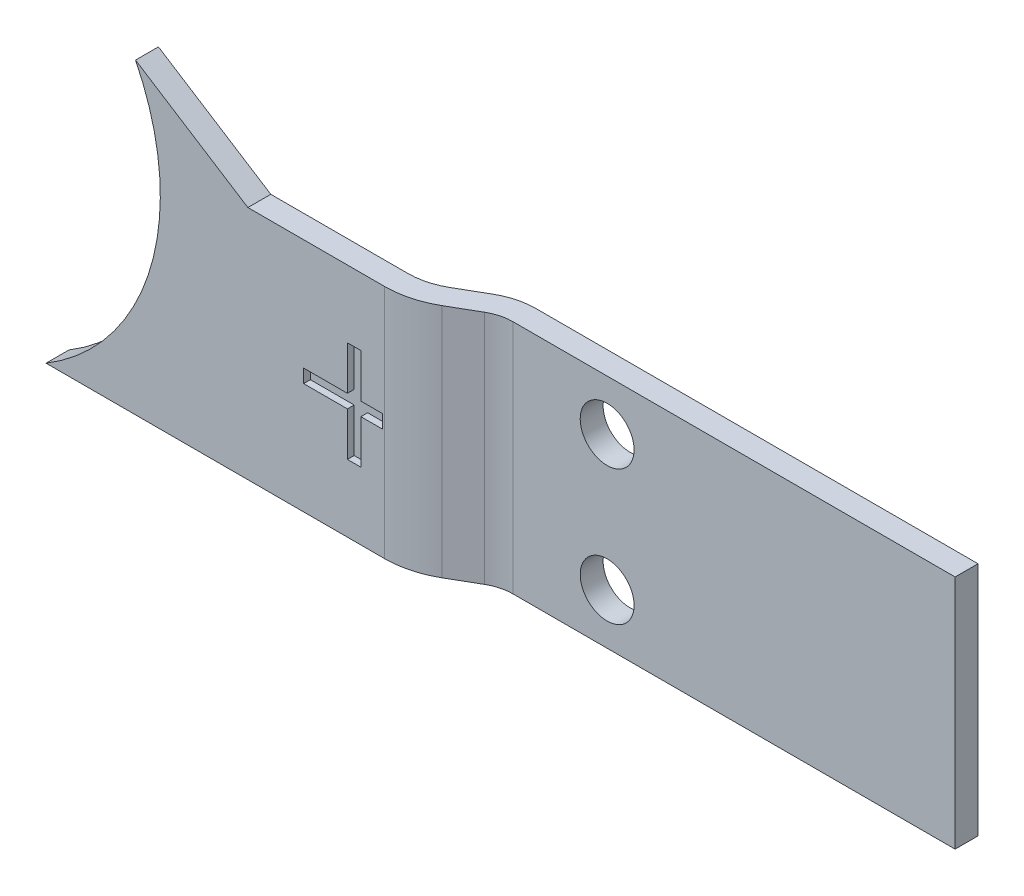
SolidWorks part; units mm, degrees
ref_plane "前视基准面" through (0, 0, 0) normal (0, 0, 1) x (1, 0, 0)
ref_plane "上视基准面" through (0, 0, 0) normal (0, 1, 0) x (1, 0, 0)
ref_plane "右视基准面" through (0, 0, 0) normal (1, 0, 0) x (0, 0, -1)
sketch "Sketch1" plane through (0, 0, 0) normal (0, 0, 1) x (1, 0, 0)
  line L0 (0, -30) -> (80, -30)
  line L1 (80, -30) -> (80, 5)
  line L2 (80, 5) -> (48, 5)
  line L4 (48, 5) -> (16.1141, 25.3049)
  arc A0 (16.1141, 25.3049) -> (0, -30) centre (0, 0) ccw
  dimension "D1" = 80
  dimension "D2" = 60
  dimension "D3" = 35
  dimension "D4" = 32
extrude "Boss-Extrude1" add sketch "Sketch1" along normal blind 3.4
sketch "Sketch2" plane through (0, 0, 3.4) normal (0, 0, 1) x (1, 0, 0)
  circle A0 centre (48, -12.5) radius 2.75
  circle A3 centre (48, -12.5) radius 2
  dimension "D2" = 5.5
sketch "Sketch3" plane through (0, 0, 3.4) normal (0, 0, 1) x (1, 0, 0)
  circle A0 centre (0, 0) radius 5
  dimension "D1" = 10
extrude "Cut-Extrude1" cut sketch "Sketch3" against normal blind 6
sketch "Sketch5" plane through (0, 0, 3.4) normal (0, 0, 1) x (1, 0, 0)
  line L0 (0, 20) -> (0, 0) construction
  line L1 (0, 0) -> (-18.1865, -10.5) construction
  arc A0 (0, 10) -> (-8.6603, -5) centre (0, 0) ccw
  arc A2 (0, 18) -> (-15.5885, -9) centre (0, 0) ccw
  arc A3 (-8.6603, -5) -> (-15.5885, -9) centre (-12.1244, -7) cw
  arc A4 (0, 18) -> (0, 10) centre (0, 14) cw
  point P4 (0, 18)
  point P6 (0, 10)
  point P8 (-8.6603, -5)
  point P9 (-15.5885, -9)
  dimension "D1" = 120
  dimension "D2" = 21
extrude "Cut-Extrude2" cut sketch "Sketch5" against normal blind 10
sketch "Sketch6" plane through (0, 0, 0) normal (0, 0, -1) x (-1, 0, 0)
  circle A0 centre (0, 0) radius 35
extrude "Cut-Extrude3" cut sketch "Sketch6" against normal blind 10
sketch "Sketch7" plane through (0, 0, 3.4) normal (0, 0, 1) x (1, 0, 0)
  line L0 (62.7754, -13.5) -> (62.7754, -20)
  line L1 (64.7754, -5) -> (62.7754, -5)
  line L2 (64.7754, -5) -> (64.7754, -11.5)
  line L3 (64.7754, -20) -> (62.7754, -20)
  line L4 (62.7754, -5) -> (62.7754, -11.5)
  line L5 (80, 5) -> (48, 5) construction
  line L7 (80, -30) -> (80, 5) construction
  line L8 (62.7754, -11.5) -> (56.2754, -11.5)
  line L9 (71.2754, -11.5) -> (64.7754, -11.5)
  line L10 (71.2754, -11.5) -> (71.2754, -13.5)
  line L11 (71.2754, -13.5) -> (64.7754, -13.5)
  line L12 (56.2754, -11.5) -> (56.2754, -13.5)
  line L17 (62.7754, -13.5) -> (56.2754, -13.5)
  line L18 (63.9087, -13.5) -> (63.642, -13.5)
  line L19 (64.7754, -13.5) -> (64.7754, -20)
  point P0 (63.9087, -12.5)
  point P9 (80, -12.5)
  point P10 (63.7754, -13.5)
  dimension "D1" = 15
  dimension "D2" = 2
  dimension "D3" = 0
  dimension "D4" = 2
  dimension "D5" = 15
  dimension "D6" = 16.5
extrude "Cut-Extrude4" cut sketch "Sketch7" against normal blind 1 contours L19 L11 L10 L9 L2 L1 L4 L8 L12 L17 L0 L3 region at (63.7754, -12.5, 3.4)
sketch "Sketch8" plane through (0, 0, 0) normal (0, 0, -1) x (-1, 0, 0)
  line L0 (-80, 5) -> (-48, 5) construction
  line L1 (-80, -30) -> (-68, -30)
  line L2 (-80, -30) -> (-80, 5)
  line L3 (-80, 5) -> (-68, 5)
  line L4 (-68, -30) -> (-68, 5)
  dimension "D1" = 20
extrude "Cut-Extrude5" cut sketch "Sketch8" against normal up to next
sketch "Sketch9" plane through (0, 5, 0) normal (0, 1, 0) x (1, 0, 0)
  line L0 (68, 0) -> (68.3205, 0)
  line L1 (83, 5) -> (148, 5)
  line L2 (73.3205, 1.3397) -> (77.3397, 3.6603)
  line L3 (68, -3.4) -> (68.3205, -3.4)
  line L4 (75.0205, -1.6047) -> (79.0397, 0.7158)
  line L5 (82.3397, 5) -> (83, 5)
  line L6 (68, 0) -> (48, 0) construction
  line L7 (82.3397, 1.6) -> (83, 1.6)
  line L8 (83, 1.6) -> (148, 1.6)
  line L9 (68, 0) -> (68, -3.4)
  line L10 (148, 1.6) -> (148, 5)
  arc A0 (77.3397, 3.6603) -> (82.3397, 5) centre (82.3397, -5) cw
  arc A1 (68.3205, 0) -> (73.3205, 1.3397) centre (68.3205, 10) ccw
  arc A2 (68.3205, -3.4) -> (75.0205, -1.6047) centre (68.3205, 10) ccw
  arc A3 (79.0397, 0.7158) -> (82.3397, 1.6) centre (82.3397, -5) cw
  point P11 (68, 0)
  dimension "D1" = 15
  dimension "D4" = 10
  dimension "D2" = 5
  dimension "D3" = 150
  dimension "D6" = 65
  dimension "D5" = 3.4
extrude "Boss-Extrude2" add sketch "Sketch9" against normal up to surface (35 mm away) up to face at (43.0139, -30, 1.7)
sketch "Sketch10" plane through (0, 0, -5) normal (0, 0, -1) x (-1, 0, 0)
  line L0 (-96.3397, 5) -> (-96.3397, -30) construction
  line L1 (-148, 5) -> (-82.3397, 5) construction
  line L2 (-82.3397, -30) -> (-148, -30) construction
  line L3 (-82.3397, -30) -> (-82.3397, 5) construction
  line L4 (-82.3397, -12.5) -> (-106.6658, -12.5) construction
  circle A0 centre (-96.3397, -2.5) radius 4
  circle A1 centre (-96.3397, -22.5) radius 4
  dimension "D2" = 10
  dimension "D1" = 14
extrude "Cut-Extrude6" cut sketch "Sketch10" against normal blind 10
